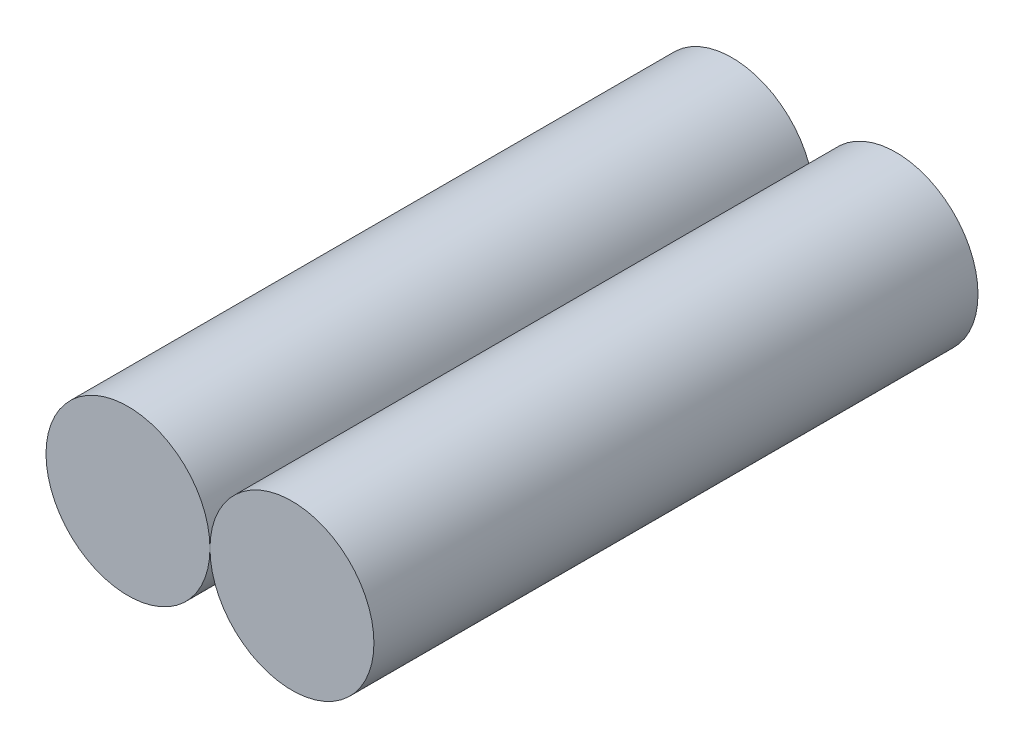
SolidWorks part; units mm, degrees
ref_plane "Front Plane" through (0, 0, 0) normal (0, 0, 1) x (1, 0, 0)
ref_plane "Top Plane" through (0, 0, 0) normal (0, 1, 0) x (1, 0, 0)
ref_plane "Right Plane" through (0, 0, 0) normal (1, 0, 0) x (0, 0, -1)
sketch "Sketch1" plane through (0, 0, 0) normal (0, 0, 1) x (1, 0, 0)
  line L0 (0, 0) -> (28.1527, 0) construction
  circle A0 centre (0, 0) radius 9.5
  circle A2 centre (-19, 0) radius 9.5
  dimension "D1" = 19
extrude "Boss-Extrude1" add sketch "Sketch1" along normal blind 35 and the other way blind 35 contours A2 L0 | A0 L0 | L0 | L0 | L0 A0 | L0 A2 | L0 | L0 | L0 | L0 region at (0, -9.2313, 0) region at (-19, 0, 0)
